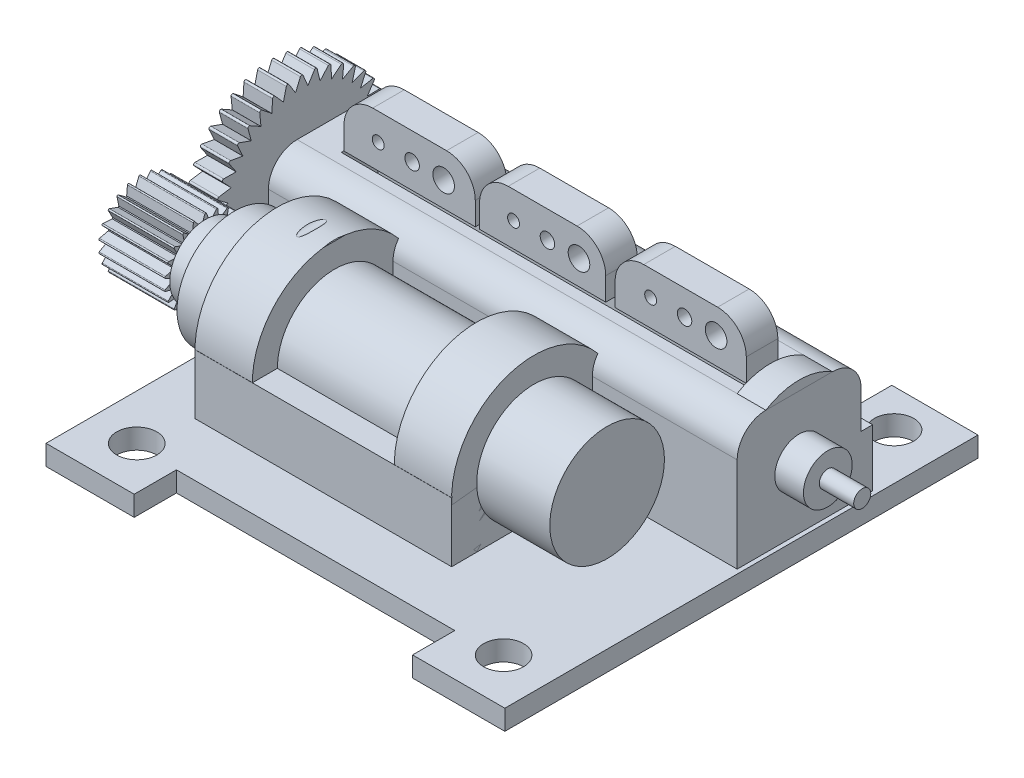
SolidWorks part; units mm, degrees
ref_plane "Front Plane" through (0, 0, 0) normal (0, 0, 1) x (1, 0, 0)
ref_plane "Top Plane" through (0, 0, 0) normal (0, 1, 0) x (1, 0, 0)
ref_plane "Right Plane" through (0, 0, 0) normal (1, 0, 0) x (0, 0, -1)
sketch "Sketch1" plane through (0, 0, 0) normal (0, 1, 0) x (1, 0, 0)
  line L0 (-6.8023, 1428.1887) -> (2681.1977, 1428.1887) construction
  line L1 (-145.6965, -70.1993) -> (-145.6965, -68.7266)
  line L2 (-148.7723, -53.6993) -> (-145.6965, -53.6993)
  line L3 (-148.7723, -70.1993) -> (-148.7723, -53.6993)
  line L4 (-135.7771, -53.6993) -> (-132.7723, -53.6993)
  line L5 (-132.7723, -70.1993) -> (-132.7723, -53.6993)
  line L6 (-145.6965, -68.7266) -> (-135.9898, -68.7266)
  line L7 (-135.9898, -68.7266) -> (-135.9898, -70.1993)
  line L8 (-135.7771, -53.6993) -> (-135.7771, -55.0042)
  line L9 (-135.7771, -55.0042) -> (-145.6965, -55.0042)
  line L10 (-145.6965, -55.0042) -> (-145.6965, -53.6993)
  line L11 (-132.7723, -70.1993) -> (-135.9898, -70.1993)
  line L12 (-145.6965, -70.1993) -> (-148.7723, -70.1993)
  circle A0 centre (-147.1858, -68.6202) radius 0.7
  circle A1 centre (-134.3942, -68.6202) radius 0.6981
  circle A2 centre (-147.1858, -55.0042) radius 0.7026
  circle A3 centre (-134.3942, -55.0042) radius 0.6863
extrude "Boss-Extrude1" add sketch "Sketch1" along normal blind 0.7
sketch "Sketch2" plane through (0, 0.7, 0) normal (0, 1, 0) x (1, 0, 0)
  line L1 (-132.9205, -61.9493) -> (-149.2665, -61.9493)
  line L3 (-132.9205, -57.6262) -> (-149.2665, -57.6262)
  line L4 (-149.2665, -61.9493) -> (-149.2665, -57.6262)
  line L5 (-132.9205, -61.9493) -> (-132.9205, -57.6262)
extrude "Boss-Extrude2" add sketch "Sketch2" along normal blind 4.3 separate body
ref_plane "Plane1" through (-135.4205, 0, 0) normal (1, 0, 0) x (0, 0, -1)
sketch "Sketch3" plane through (-135.4205, 0, 0) normal (1, 0, 0) x (0, 0, -1)
  circle A0 centre (-63.9845, 2.7802) radius 1.9992
extrude "Boss-Extrude3" add sketch "Sketch3" against normal blind 13 separate body
sketch "Sketch5" plane through (-148.4205, 0, 0) normal (-1, 0, 0) x (0, 0, 1)
  circle A0 centre (63.9845, 2.7802) radius 1.25
extrude "Boss-Extrude4" add sketch "Sketch5" along normal blind 1
sketch "Sketch6" plane through (-149.4205, 0, 0) normal (-1, 0, 0) x (0, 0, 1)
  line L0 (63.9565, 4.2027) -> (63.8404, 3.9001)
  line L1 (64.1285, 3.9001) -> (64.1618, 3.8954)
  line L2 (64.0125, 4.2027) -> (64.1285, 3.9001)
  line L3 (64.3583, 4.1529) -> (64.1618, 3.8954)
  line L4 (64.4121, 4.1372) -> (64.4382, 3.8142)
  line L5 (64.7299, 3.992) -> (64.4688, 3.8002)
  line L6 (64.7771, 3.9617) -> (64.7111, 3.6445)
  line L7 (65.0411, 3.7329) -> (64.7365, 3.6225)
  line L8 (65.0778, 3.6906) -> (64.9252, 3.4047)
  line L9 (65.2667, 3.3966) -> (64.9433, 3.3765)
  line L10 (65.29, 3.3457) -> (65.063, 3.1144)
  line L11 (65.3884, 3.0104) -> (65.0725, 3.0822)
  line L12 (65.3964, 2.9549) -> (65.1135, 2.797)
  line L13 (65.3964, 2.6055) -> (65.1135, 2.7635)
  line L14 (65.3884, 2.5501) -> (65.0725, 2.4783)
  line L15 (65.29, 2.2148) -> (65.063, 2.4461)
  line L16 (65.2667, 2.1639) -> (64.9433, 2.184)
  line L17 (65.0778, 1.8699) -> (64.9252, 2.1557)
  line L18 (65.0411, 1.8276) -> (64.7365, 1.938)
  line L19 (64.7771, 1.5988) -> (64.7111, 1.916)
  line L20 (64.7299, 1.5685) -> (64.4688, 1.7603)
  line L21 (64.4121, 1.4233) -> (64.4382, 1.7463)
  line L22 (64.3583, 1.4075) -> (64.1618, 1.6651)
  line L23 (64.0125, 1.3578) -> (64.1285, 1.6604)
  line L24 (63.9565, 1.3578) -> (63.8404, 1.6604)
  line L25 (63.6106, 1.4075) -> (63.8072, 1.6651)
  line L26 (63.5569, 1.4233) -> (63.5308, 1.7463)
  line L27 (63.239, 1.5685) -> (63.5002, 1.7603)
  line L28 (63.1919, 1.5988) -> (63.2578, 1.916)
  line L29 (62.9278, 1.8276) -> (63.2325, 1.938)
  line L30 (62.8911, 1.8699) -> (63.0438, 2.1557)
  line L31 (62.7022, 2.1639) -> (63.0256, 2.184)
  line L32 (62.679, 2.2148) -> (62.906, 2.4461)
  line L33 (62.5805, 2.5501) -> (62.8965, 2.4783)
  line L34 (62.5725, 2.6055) -> (62.8555, 2.7635)
  line L35 (62.5725, 2.9549) -> (62.8555, 2.797)
  line L36 (62.5805, 3.0104) -> (62.8965, 3.0822)
  line L37 (62.679, 3.3457) -> (62.906, 3.1144)
  line L38 (62.7022, 3.3966) -> (63.0256, 3.3765)
  line L39 (62.8911, 3.6906) -> (63.0438, 3.4047)
  line L40 (62.9278, 3.7329) -> (63.2325, 3.6225)
  line L41 (63.1919, 3.9617) -> (63.2578, 3.6445)
  line L42 (63.239, 3.992) -> (63.5002, 3.8002)
  line L43 (63.5569, 4.1372) -> (63.5308, 3.8142)
  line L44 (63.6106, 4.1529) -> (63.8072, 3.8954)
  line L45 (64.4382, 3.8142) -> (64.4688, 3.8002)
  line L46 (64.7111, 3.6445) -> (64.7365, 3.6225)
  line L47 (64.9252, 3.4047) -> (64.9433, 3.3765)
  line L48 (65.063, 3.1144) -> (65.0725, 3.0822)
  line L49 (65.1135, 2.797) -> (65.1135, 2.7635)
  line L50 (65.0725, 2.4783) -> (65.063, 2.4461)
  line L51 (64.9433, 2.184) -> (64.9252, 2.1557)
  line L52 (64.7365, 1.938) -> (64.7111, 1.916)
  line L53 (64.4688, 1.7603) -> (64.4382, 1.7463)
  line L54 (64.1618, 1.6651) -> (64.1285, 1.6604)
  line L55 (63.8404, 1.6604) -> (63.8072, 1.6651)
  line L56 (63.5308, 1.7463) -> (63.5002, 1.7603)
  line L57 (63.2578, 1.916) -> (63.2325, 1.938)
  line L58 (63.0438, 2.1557) -> (63.0256, 2.184)
  line L59 (62.906, 2.4461) -> (62.8965, 2.4783)
  line L60 (62.8555, 2.7635) -> (62.8555, 2.797)
  line L61 (62.8965, 3.0822) -> (62.906, 3.1144)
  line L62 (63.0256, 3.3765) -> (63.0438, 3.4047)
  line L63 (63.2325, 3.6225) -> (63.2578, 3.6445)
  line L64 (63.8072, 3.8954) -> (63.8404, 3.9001)
  line L65 (63.5002, 3.8002) -> (63.5308, 3.8142)
  arc A1 (63.9565, 4.2027) -> (64.0125, 4.2027) centre (63.9845, 4.1919) cw
  arc A3 (64.3583, 4.1529) -> (64.4121, 4.1372) centre (64.3822, 4.1347) cw
  arc A4 (64.7299, 3.992) -> (64.7771, 3.9617) centre (64.7477, 3.9678) cw
  arc A5 (65.0411, 3.7329) -> (65.0778, 3.6906) centre (65.0514, 3.7047) cw
  arc A6 (65.2667, 3.3966) -> (65.29, 3.3457) centre (65.2686, 3.3667) cw
  arc A7 (65.3884, 3.0104) -> (65.3964, 2.9549) centre (65.3818, 2.9811) cw
  arc A8 (65.3964, 2.6055) -> (65.3884, 2.5501) centre (65.3818, 2.5793) cw
  arc A9 (65.29, 2.2148) -> (65.2667, 2.1639) centre (65.2686, 2.1938) cw
  arc A10 (65.0778, 1.8699) -> (65.0411, 1.8276) centre (65.0514, 1.8558) cw
  arc A11 (64.7771, 1.5988) -> (64.7299, 1.5685) centre (64.7477, 1.5927) cw
  arc A12 (64.4121, 1.4233) -> (64.3583, 1.4075) centre (64.3822, 1.4257) cw
  arc A13 (64.0125, 1.3578) -> (63.9565, 1.3578) centre (63.9845, 1.3686) cw
  arc A14 (63.6106, 1.4075) -> (63.5569, 1.4233) centre (63.5868, 1.4257) cw
  arc A15 (63.239, 1.5685) -> (63.1919, 1.5988) centre (63.2213, 1.5927) cw
  arc A16 (62.9278, 1.8276) -> (62.8911, 1.8699) centre (62.9176, 1.8558) cw
  arc A17 (62.7022, 2.1639) -> (62.679, 2.2148) centre (62.7004, 2.1938) cw
  arc A18 (62.5805, 2.5501) -> (62.5725, 2.6055) centre (62.5872, 2.5793) cw
  arc A19 (62.5725, 2.9549) -> (62.5805, 3.0104) centre (62.5872, 2.9811) cw
  arc A20 (62.679, 3.3457) -> (62.7022, 3.3966) centre (62.7004, 3.3667) cw
  arc A21 (62.8911, 3.6906) -> (62.9278, 3.7329) centre (62.9176, 3.7047) cw
  arc A22 (63.1919, 3.9617) -> (63.239, 3.992) centre (63.2213, 3.9678) cw
  arc A23 (63.5569, 4.1372) -> (63.6106, 4.1529) centre (63.5868, 4.1347) cw
  point P121 (63.9845, 2.7802)
  dimension "D1" = 0.03
  dimension "D2" = 22
extrude "Boss-Extrude5" add sketch "Sketch6" along normal blind 2.3
sketch "Sketch7" plane through (-149.2665, 0, 0) normal (-1, 0, 0) x (0, 0, 1)
  circle A0 centre (59.7878, 2.85) radius 1.0013
extrude "Boss-Extrude6" add sketch "Sketch7" along normal blind 1
sketch "Sketch8" plane through (-150.2665, 0, 0) normal (-1, 0, 0) x (0, 0, 1)
  line L0 (59.7878, 2.85) -> (59.7878, 5.95) construction
  line L1 (59.7417, 5.8403) -> (59.5736, 5.4404)
  line L2 (59.8339, 5.8403) -> (60.0019, 5.4404)
  line L3 (60.3254, 5.7919) -> (60.4254, 5.3698)
  line L4 (60.2345, 5.8071) -> (60.0029, 5.4403)
  line L5 (60.8023, 5.6633) -> (60.8314, 5.2304)
  line L6 (60.7151, 5.6932) -> (60.4263, 5.3695)
  line L7 (61.2515, 5.4579) -> (61.209, 5.0262)
  line L8 (61.1704, 5.5017) -> (60.8323, 5.23)
  line L9 (61.6608, 5.1813) -> (61.5478, 4.7625)
  line L10 (61.588, 5.238) -> (61.2098, 5.0256)
  line L11 (62.019, 4.8412) -> (61.8385, 4.4467)
  line L12 (61.9565, 4.9091) -> (61.5485, 4.7618)
  line L13 (62.3163, 4.4468) -> (62.0734, 4.0874)
  line L14 (62.2658, 4.524) -> (61.8391, 4.4459)
  line L15 (62.5446, 4.0088) -> (62.2459, 3.6943)
  line L16 (62.5076, 4.0932) -> (62.0738, 4.0865)
  line L17 (62.6977, 3.5392) -> (62.3513, 3.2781)
  line L18 (62.6751, 3.6286) -> (62.2462, 3.6933)
  line L19 (62.7715, 3.0508) -> (62.3868, 2.8503)
  line L20 (62.7639, 3.1427) -> (62.3514, 3.2772)
  line L21 (62.7638, 2.557) -> (62.3514, 2.4225)
  line L22 (62.7715, 2.6488) -> (62.3868, 2.8493)
  line L23 (62.675, 2.0711) -> (62.2461, 2.0063)
  line L24 (62.6976, 2.1604) -> (62.3512, 2.4215)
  line L25 (62.5074, 1.6064) -> (62.0737, 1.6132)
  line L26 (62.5445, 1.6909) -> (62.2457, 2.0054)
  line L27 (62.2656, 1.1757) -> (61.8389, 1.2538)
  line L28 (62.3161, 1.2529) -> (62.0732, 1.6123)
  line L29 (61.9563, 0.7907) -> (61.5482, 0.9379)
  line L30 (62.0187, 0.8585) -> (61.8383, 1.253)
  line L31 (61.5877, 0.4618) -> (61.2095, 0.6742)
  line L32 (61.6605, 0.5185) -> (61.5475, 0.9373)
  line L33 (61.1701, 0.1981) -> (60.832, 0.4698)
  line L34 (61.2512, 0.242) -> (61.2086, 0.6737)
  line L35 (60.7148, 0.0067) -> (60.426, 0.3304)
  line L36 (60.802, 0.0367) -> (60.831, 0.4695)
  line L37 (60.2341, -0.1071) -> (60.0025, 0.2597)
  line L38 (60.3251, -0.0919) -> (60.425, 0.3302)
  line L39 (59.7413, -0.1403) -> (59.5733, 0.2596)
  line L40 (59.8335, -0.1403) -> (60.0015, 0.2596)
  line L41 (59.2497, -0.0919) -> (59.1498, 0.3302)
  line L42 (59.3407, -0.107) -> (59.5723, 0.2598)
  line L43 (58.7729, 0.0368) -> (58.7438, 0.4696)
  line L44 (58.8601, 0.0068) -> (59.1489, 0.3305)
  line L45 (58.3237, 0.2422) -> (58.3662, 0.6739)
  line L46 (58.4047, 0.1983) -> (58.7429, 0.47)
  line L47 (57.9144, 0.5187) -> (58.0274, 0.9375)
  line L48 (57.9871, 0.4621) -> (58.3654, 0.6744)
  line L49 (57.5562, 0.8588) -> (57.7366, 1.2533)
  line L50 (57.6187, 0.791) -> (58.0267, 0.9382)
  line L51 (57.2589, 1.2532) -> (57.5018, 1.6126)
  line L52 (57.3093, 1.176) -> (57.736, 1.2541)
  line L53 (57.0306, 1.6912) -> (57.3293, 2.0058)
  line L54 (57.0676, 1.6068) -> (57.5013, 1.6135)
  line L55 (56.8774, 2.1608) -> (57.2239, 2.4219)
  line L56 (56.9001, 2.0714) -> (57.329, 2.0067)
  line L57 (56.8037, 2.6492) -> (57.1884, 2.8497)
  line L58 (56.8113, 2.5573) -> (57.2237, 2.4229)
  line L59 (56.8113, 3.1431) -> (57.2238, 3.2775)
  line L60 (56.8037, 3.0512) -> (57.1884, 2.8507)
  line L61 (56.9002, 3.629) -> (57.3291, 3.6937)
  line L62 (56.8775, 3.5396) -> (57.224, 3.2785)
  line L63 (57.0677, 4.0936) -> (57.5015, 4.0868)
  line L64 (57.0307, 4.0092) -> (57.3294, 3.6946)
  line L65 (57.3095, 4.5243) -> (57.7362, 4.4462)
  line L66 (57.2591, 4.4471) -> (57.502, 4.0877)
  line L67 (57.6189, 4.9093) -> (58.0269, 4.7621)
  line L68 (57.5565, 4.8415) -> (57.7369, 4.447)
  line L69 (57.9874, 5.2382) -> (58.3657, 5.0258)
  line L70 (57.9147, 5.1816) -> (58.0277, 4.7628)
  line L71 (58.4051, 5.5019) -> (58.7432, 5.2302)
  line L72 (58.324, 5.458) -> (58.3665, 5.0263)
  line L73 (58.8604, 5.6933) -> (59.1492, 5.3696)
  line L74 (58.7732, 5.6634) -> (58.7441, 5.2306)
  line L75 (59.341, 5.8071) -> (59.5726, 5.4403)
  line L76 (59.2501, 5.792) -> (59.1502, 5.3698)
  line L77 (60.0029, 5.4403) -> (60.0019, 5.4404)
  line L78 (59.5736, 5.4404) -> (59.5726, 5.4403)
  line L79 (60.4263, 5.3695) -> (60.4254, 5.3698)
  line L80 (60.8323, 5.23) -> (60.8314, 5.2304)
  line L81 (61.2098, 5.0256) -> (61.209, 5.0262)
  line L82 (61.5485, 4.7618) -> (61.5478, 4.7625)
  line L83 (61.8391, 4.4459) -> (61.8385, 4.4467)
  line L84 (62.0738, 4.0865) -> (62.0734, 4.0874)
  line L85 (62.2462, 3.6933) -> (62.2459, 3.6943)
  line L86 (62.3514, 3.2772) -> (62.3513, 3.2781)
  line L87 (62.3868, 2.8493) -> (62.3868, 2.8503)
  line L88 (62.3512, 2.4215) -> (62.3514, 2.4225)
  line L89 (62.2457, 2.0054) -> (62.2461, 2.0063)
  line L90 (62.0732, 1.6123) -> (62.0737, 1.6132)
  line L91 (61.8383, 1.253) -> (61.8389, 1.2538)
  line L92 (61.5475, 0.9373) -> (61.5482, 0.9379)
  line L93 (61.2086, 0.6737) -> (61.2095, 0.6742)
  line L94 (60.831, 0.4695) -> (60.832, 0.4698)
  line L95 (60.425, 0.3302) -> (60.426, 0.3304)
  line L96 (60.0015, 0.2596) -> (60.0025, 0.2597)
  line L97 (59.5723, 0.2598) -> (59.5733, 0.2596)
  line L98 (59.1489, 0.3305) -> (59.1498, 0.3302)
  line L99 (58.7429, 0.47) -> (58.7438, 0.4696)
  line L100 (58.3654, 0.6744) -> (58.3662, 0.6739)
  line L101 (58.0267, 0.9382) -> (58.0274, 0.9375)
  line L102 (57.736, 1.2541) -> (57.7366, 1.2533)
  line L103 (57.5013, 1.6135) -> (57.5018, 1.6126)
  line L104 (57.329, 2.0067) -> (57.3293, 2.0058)
  line L105 (57.2237, 2.4229) -> (57.2239, 2.4219)
  line L106 (57.1884, 2.8507) -> (57.1884, 2.8497)
  line L107 (57.224, 3.2785) -> (57.2238, 3.2775)
  line L108 (57.3294, 3.6946) -> (57.3291, 3.6937)
  line L109 (57.502, 4.0877) -> (57.5015, 4.0868)
  line L110 (57.7369, 4.447) -> (57.7362, 4.4462)
  line L111 (58.0277, 4.7628) -> (58.0269, 4.7621)
  line L112 (58.3665, 5.0263) -> (58.3657, 5.0258)
  line L113 (58.7441, 5.2306) -> (58.7432, 5.2302)
  line L115 (59.1502, 5.3698) -> (59.1492, 5.3696)
  circle A0 centre (59.7878, 2.85) radius 3.1 construction
  arc A1 (60.3254, 5.7919) -> (60.2345, 5.8071) centre (60.2768, 5.7804) ccw
  arc A2 (59.8339, 5.8403) -> (59.7417, 5.8403) centre (59.7878, 5.8209) ccw
  arc A3 (60.8023, 5.6633) -> (60.7151, 5.6932) centre (60.7524, 5.6599) ccw
  arc A4 (61.2515, 5.4579) -> (61.1704, 5.5017) centre (61.2017, 5.4628) ccw
  arc A5 (61.6608, 5.1813) -> (61.588, 5.238) centre (61.6125, 5.1944) ccw
  arc A6 (62.019, 4.8412) -> (61.9565, 4.9091) centre (61.9735, 4.862) ccw
  arc A7 (62.3163, 4.4468) -> (62.2658, 4.524) centre (62.2748, 4.4748) ccw
  arc A8 (62.5446, 4.0088) -> (62.5076, 4.0932) centre (62.5083, 4.0433) ccw
  arc A9 (62.6977, 3.5392) -> (62.6751, 3.6286) centre (62.6676, 3.5792) ccw
  arc A10 (62.7715, 3.0508) -> (62.7639, 3.1427) centre (62.7484, 3.0952) ccw
  arc A11 (62.7638, 2.557) -> (62.7715, 2.6488) centre (62.7483, 2.6045) ccw
  arc A12 (62.675, 2.0711) -> (62.6976, 2.1604) centre (62.6676, 2.1205) ccw
  arc A13 (62.5074, 1.6064) -> (62.5445, 1.6909) centre (62.5082, 1.6564) ccw
  arc A14 (62.2656, 1.1757) -> (62.3161, 1.2529) centre (62.2746, 1.2249) ccw
  arc A15 (61.9563, 0.7907) -> (62.0187, 0.8585) centre (61.9732, 0.8377) ccw
  arc A16 (61.5877, 0.4618) -> (61.6605, 0.5185) centre (61.6122, 0.5054) ccw
  arc A17 (61.1701, 0.1981) -> (61.2512, 0.242) centre (61.2014, 0.2371) ccw
  arc A18 (60.7148, 0.0067) -> (60.802, 0.0367) centre (60.7521, 0.04) ccw
  arc A19 (60.2341, -0.1071) -> (60.3251, -0.0919) centre (60.2764, -0.0804) ccw
  arc A20 (59.7413, -0.1403) -> (59.8335, -0.1403) centre (59.7874, -0.1209) ccw
  arc A21 (59.2497, -0.0919) -> (59.3407, -0.107) centre (59.2984, -0.0804) ccw
  arc A22 (58.7729, 0.0368) -> (58.8601, 0.0068) centre (58.8228, 0.0401) ccw
  arc A23 (58.3237, 0.2422) -> (58.4047, 0.1983) centre (58.3734, 0.2373) ccw
  arc A24 (57.9144, 0.5187) -> (57.9871, 0.4621) centre (57.9627, 0.5057) ccw
  arc A25 (57.5562, 0.8588) -> (57.6187, 0.791) centre (57.6017, 0.838) ccw
  arc A26 (57.2589, 1.2532) -> (57.3093, 1.176) centre (57.3003, 1.2252) ccw
  arc A27 (57.0306, 1.6912) -> (57.0676, 1.6068) centre (57.0668, 1.6568) ccw
  arc A28 (56.8774, 2.1608) -> (56.9001, 2.0714) centre (56.9075, 2.1209) ccw
  arc A29 (56.8037, 2.6492) -> (56.8113, 2.5573) centre (56.8268, 2.6049) ccw
  arc A30 (56.8113, 3.1431) -> (56.8037, 3.0512) centre (56.8268, 3.0955) ccw
  arc A31 (56.9002, 3.629) -> (56.8775, 3.5396) centre (56.9076, 3.5795) ccw
  arc A32 (57.0677, 4.0936) -> (57.0307, 4.0092) centre (57.067, 4.0436) ccw
  arc A33 (57.3095, 4.5243) -> (57.2591, 4.4471) centre (57.3005, 4.4751) ccw
  arc A34 (57.6189, 4.9093) -> (57.5565, 4.8415) centre (57.6019, 4.8623) ccw
  arc A35 (57.9874, 5.2382) -> (57.9147, 5.1816) centre (57.963, 5.1946) ccw
  arc A36 (58.4051, 5.5019) -> (58.324, 5.458) centre (58.3737, 5.4629) ccw
  arc A37 (58.8604, 5.6933) -> (58.7732, 5.6634) centre (58.8231, 5.66) ccw
  arc A38 (59.341, 5.8071) -> (59.2501, 5.792) centre (59.2988, 5.7804) ccw
  point P197 (59.7876, 2.85)
  dimension "D1" = 0.05
  dimension "D2" = 38
extrude "Boss-Extrude7" add sketch "Sketch8" along normal blind 1
sketch "Sketch9" plane through (0, 5, 0) normal (0, 1, 0) x (1, 0, 0)
  line L1 (-148.1095, -59.2908) -> (-134.0519, -59.2908)
  line L2 (-148.1095, -59.2908) -> (-148.1095, -60.5659)
  line L3 (-148.1095, -60.5659) -> (-134.0519, -60.5659)
  line L4 (-134.0519, -59.2908) -> (-134.0519, -60.5659)
extrude "Cut-Extrude1" cut sketch "Sketch9" against normal blind 3
sketch "Sketch10" plane through (0, 5, 0) normal (0, 1, 0) x (1, 0, 0)
  line L1 (-138.6477, -59.3784) -> (-134.0728, -59.3784)
  line L2 (-138.6477, -59.3784) -> (-138.6477, -60.4784)
  line L3 (-138.6477, -60.4784) -> (-134.0728, -60.4784)
  line L4 (-134.0728, -59.3784) -> (-134.0728, -60.4784)
extrude "Boss-Extrude8" add sketch "Sketch10" along normal blind 1.8 separate body
sketch "Sketch11" plane through (0, 0, 0) normal (0, -1, 0) x (1, 0, 0)
  line L0 (-0.1175, 1177.0277) -> (2687.8825, 1177.0277) construction
  line L2 (-137.4415, 58.9786) -> (-135.6579, 58.9786)
  line L3 (-137.4415, 58.9786) -> (-137.4415, 55.8886)
  line L4 (-137.4415, 55.8886) -> (-135.6579, 55.8886)
  line L5 (-135.6579, 58.9786) -> (-135.6579, 55.8886)
extrude "Boss-Extrude9" add sketch "Sketch11" along normal blind 1.7
sketch "Sketch12" plane through (0, 0, 0) normal (0, -1, 0) x (1, 0, 0)
  line L1 (-144.8608, 67.6738) -> (-140.6627, 67.6738)
  line L2 (-144.8608, 67.6738) -> (-144.8608, 63.4439)
  line L3 (-144.8608, 63.4439) -> (-140.6627, 63.4439)
  line L4 (-140.6627, 67.6738) -> (-140.6627, 63.4439)
  line L5 (-144.8608, 60.1387) -> (-141.9705, 60.1387)
  line L6 (-144.8608, 60.1387) -> (-144.8608, 56.9974)
  line L7 (-144.8608, 56.9974) -> (-141.9705, 56.9974)
  line L8 (-141.9705, 60.1387) -> (-141.9705, 56.9974)
  line L9 (-137.8261, 64.4942) -> (-135.028, 64.4942)
  line L10 (-137.8261, 64.4942) -> (-137.8261, 62.9368)
  line L11 (-137.8261, 62.9368) -> (-135.028, 62.9368)
  line L12 (-135.028, 64.4942) -> (-135.028, 62.9368)
  line L13 (-143.4157, 62.0129) -> (-140.2547, 62.0129)
  line L14 (-143.4157, 62.0129) -> (-143.4157, 61.0098)
  line L15 (-143.4157, 61.0098) -> (-140.2547, 61.0098)
  line L16 (-140.2547, 62.0129) -> (-140.2547, 61.0098)
extrude "Boss-Extrude10" add sketch "Sketch12" along normal blind 1
sketch "Sketch13" plane through (-132.9205, 0, 0) normal (1, 0, 0) x (0, 0, -1)
  circle A0 centre (-59.7878, 2.85) radius 0.85
extrude "Boss-Extrude11" add sketch "Sketch13" along normal blind 1
sketch "Sketch14" plane through (-131.9205, 0, 0) normal (1, 0, 0) x (0, 0, -1)
  circle A0 centre (-59.7878, 2.85) radius 0.2977
extrude "Boss-Extrude12" add sketch "Sketch14" along normal blind 1.2
sketch "Sketch15" plane through (0, 0.7, 0) normal (0, 1, 0) x (1, 0, 0)
  line L1 (-144.8933, -61.946) -> (-146.5227, -61.946) construction
  line L2 (-144.8933, -61.946) -> (-144.8933, -66.8562) construction
  line L3 (-144.8933, -66.8562) -> (-146.5227, -66.8562) construction
  line L4 (-146.5227, -61.946) -> (-146.5227, -66.8562) construction
  line L5 (-137.9662, -61.946) -> (-140.0849, -61.946) construction
  line L6 (-137.9662, -61.946) -> (-137.9662, -66.8562) construction
  line L7 (-137.9662, -66.8562) -> (-140.0849, -66.8562) construction
  line L8 (-140.0849, -61.946) -> (-140.0849, -66.8562) construction
ref_plane "Plane2" through (-137.9705, 0, 0) normal (1, 0, 0) x (0, 0, -1)
sketch "Sketch16" plane through (-137.9705, 0, 0) normal (1, 0, 0) x (0, 0, -1)
  line L0 (-61.9853, 0.7187) -> (-65.9837, 0.7187)
  circle A1 centre (-63.9845, 2.7802) radius 1.9992
  arc A2 (-61.9853, 0.7187) -> (-65.9837, 0.7187) centre (-63.9845, 2.7802) ccw
extrude "Boss-Extrude13" add sketch "Sketch16" against normal blind 2
ref_plane "Plane3" through (-144.9205, 0, 0) normal (1, 0, 0) x (0, 0, -1)
sketch "Sketch17" plane through (-144.9205, 0, 0) normal (1, 0, 0) x (0, 0, -1)
  line L0 (-65.9837, 0.7187) -> (-62.0047, 0.7)
  line L1 (-61.946, 0.7) -> (-66.8562, 0.7) construction
  circle A1 centre (-63.9845, 2.7802) radius 1.9992
  arc A2 (-62.0047, 0.7) -> (-65.9837, 0.7187) centre (-63.9845, 2.7802) ccw
extrude "Boss-Extrude17" add sketch "Sketch17" against normal blind 2 separate body
sketch "Sketch19" plane through (0, 0, 59.3784) normal (0, 0, -1) x (-1, 0, 0)
  line L0 (-1220.0238, -401.0794) -> (-117.3572, -401.0794) construction
sketch "Sketch20" plane through (0, 0, 59.3784) normal (0, 0, -1) x (-1, 0, 0)
  line L0 (134.0728, 5) -> (134.0728, 5.8611) construction
  line L1 (135.0728, 6.8611) -> (146.9748, 6.8611) construction
  line L2 (147.9748, 5.8611) -> (147.9748, 5) construction
  line L3 (134.0519, 5) -> (148.1095, 5) construction
  line L4 (147.9748, 5) -> (134.0728, 5) construction
  line L5 (135.1265, 5.9211) -> (135.1265, 6.8611) construction
  line L6 (136.2269, 5.9211) -> (136.2269, 6.8611) construction
  line L7 (137.408, 5.9211) -> (137.408, 6.8611) construction
  arc A0 (147.9748, 5.8611) -> (146.9748, 6.8611) centre (146.9748, 5.8611) ccw construction
  arc A1 (135.0728, 6.8611) -> (134.0728, 5.8611) centre (135.0728, 5.8611) ccw construction
  circle A2 centre (137.408, 5.9211) radius 0.2076
  circle A3 centre (136.2269, 5.9211) radius 0.2526
  circle A4 centre (135.1265, 5.9211) radius 0.3768
  dimension "D1" = 1
fillet "Fillet1" radius 1 2 edges at (-138.6477, 6.8, 59.9284) (-134.0728, 6.8, 59.9284)
extrude "Cut-Extrude2" cut sketch "Sketch20" against normal blind 2
sketch "Sketch23" plane through (0, 5, 0) normal (0, 1, 0) x (1, 0, 0)
  line L0 (-148.0995, -59.3784) -> (-143.5246, -59.3784)
  line L1 (-148.0995, -59.3784) -> (-148.0995, -60.4784)
  line L2 (-148.0995, -60.4784) -> (-143.5246, -60.4784)
  line L3 (-143.5246, -59.3784) -> (-143.5246, -60.4784)
extrude "Boss-Extrude18" add sketch "Sketch23" along normal up to surface (1.8 mm away) up to face at (-136.3603, 6.8, 59.9284)
fillet "Fillet2" radius 1 2 edges at (-143.5246, 6.8, 59.9284) (-148.0995, 6.8, 59.9284)
sketch "Sketch24" plane through (0, 0, 59.3784) normal (0, 0, -1) x (-1, 0, 0)
  line L0 (144.6265, 5.86) -> (144.6265, 6.8) construction
  line L1 (144.5246, 6.8) -> (147.0995, 6.8) construction
  line L2 (145.7269, 5.86) -> (145.7269, 6.8) construction
  line L3 (146.908, 5.86) -> (146.908, 6.8) construction
  line L4 (144.6265, 5.86) -> (143.5264, 5.86) construction
  arc A0 (144.5246, 6.8) -> (143.5246, 5.8) centre (144.5246, 5.8) ccw construction
  circle A3 centre (146.908, 5.86) radius 0.2076
  circle A4 centre (145.7269, 5.86) radius 0.2526
  circle A5 centre (144.6265, 5.86) radius 0.3768
fillet "Fillet3" radius 1 2 edges at (-141.0935, 5, 61.9493) (-141.0935, 5, 57.6262)
sketch "Sketch26" plane through (0, 0, 57.6262) normal (0, 0, -1) x (-1, 0, 0)
  line L0 (149.2665, 4) -> (149.2665, 0.7) construction
  line L1 (132.9205, 0.7) -> (149.2665, 0.7)
  line L2 (132.9205, 0.7) -> (132.9205, 2.7)
  line L3 (132.9205, 2.7) -> (149.2665, 2.7)
  line L4 (149.2665, 0.7) -> (149.2665, 2.7)
extrude "Boss-Extrude19" add sketch "Sketch26" along normal blind 0.4
sketch "Sketch27" plane through (-132.9205, 0, 0) normal (1, 0, 0) x (0, 0, -1)
  line L1 (-60.9493, 5) -> (-58.6262, 5)
  arc A0 (-60.9493, 5) -> (-58.6262, 5) centre (-59.7878, 3.142) cw
extrude "Boss-Extrude20" add sketch "Sketch27" against normal blind 1 separate body
sketch "Sketch28" plane through (-137.9705, 0, 0) normal (1, 0, 0) x (0, 0, -1)
  line L0 (-66.8562, 2.7802) -> (-66.8562, 0.7)
  line L1 (-70.1993, 0.7) -> (-53.6993, 0.7) construction
  line L2 (-66.8562, 0.7) -> (-63.9942, 0.7093)
  line L3 (-66.8562, 2.7802) -> (-65.9837, 2.7802)
  line L4 (-65.9837, 0.7187) -> (-62.0047, 0.7) construction
  arc A0 (-61.7558, 4.5913) -> (-65.9837, 0.7187) centre (-63.9845, 2.7802) ccw construction
  circle A1 centre (-63.9845, 2.7802) radius 1.9992 construction
  circle A2 centre (-63.9845, 2.7802) radius 1.9992 construction
  arc A3 (-65.9837, 2.7802) -> (-63.9942, 0.7093) centre (-63.8686, 2.8211) ccw
extrude "Boss-Extrude22" add sketch "Sketch28" against normal up to surface (8.95 mm away) separate body up to face at (-146.9205, 2.7802, 61.9853)
sketch "Sketch29" plane through (-151.2665, 0, 0) normal (-1, 0, 0) x (0, 0, 1)
  circle A0 centre (59.7876, 2.85) radius 0.4023
extrude "Boss-Extrude23" add sketch "Sketch29" along normal blind 0.1
sketch "Sketch30" plane through (-151.7205, 0, 0) normal (-1, 0, 0) x (0, 0, 1)
  circle A0 centre (63.9845, 2.7802) radius 0.3993
extrude "Boss-Extrude24" add sketch "Sketch30" along normal blind 0.1
sketch "Sketch31" plane through (0, 5, 0) normal (0, 1, 0) x (1, 0, 0)
  line L2 (-143.3744, -59.3784) -> (-138.9744, -59.3784)
  line L3 (-143.3744, -59.3784) -> (-143.3744, -60.4784)
  line L4 (-143.3744, -60.4784) -> (-138.9744, -60.4784)
  line L5 (-138.9744, -59.3784) -> (-138.9744, -60.4784)
extrude "Boss-Extrude26" add sketch "Sketch31" along normal up to surface (1.8 mm away) separate body up to face at (-136.3603, 6.8, 59.9284)
fillet "Fillet4" radius 1 2 edges at (-138.9744, 6.8, 59.9284) (-143.3744, 6.8, 59.9284)
sketch "Sketch32" plane through (0, 0, 59.3784) normal (0, 0, -1) x (-1, 0, 0)
  line L0 (139.9076, 5.8532) -> (139.9076, 6.7932) construction
  line L1 (141.008, 5.8532) -> (141.008, 6.7932) construction
  line L2 (142.1891, 5.8532) -> (142.1891, 6.7932) construction
  line L3 (139.9076, 5.8532) -> (138.8075, 5.8532) construction
  circle A0 centre (142.1891, 5.8532) radius 0.2076
  circle A1 centre (141.008, 5.8532) radius 0.2526
  circle A2 centre (139.9076, 5.8532) radius 0.3768
extrude "Cut-Extrude4" cut sketch "Sketch32" against normal up to next (1.1 mm away)
extrude "Cut-Extrude5" cut sketch "Sketch24" against normal blind 10
